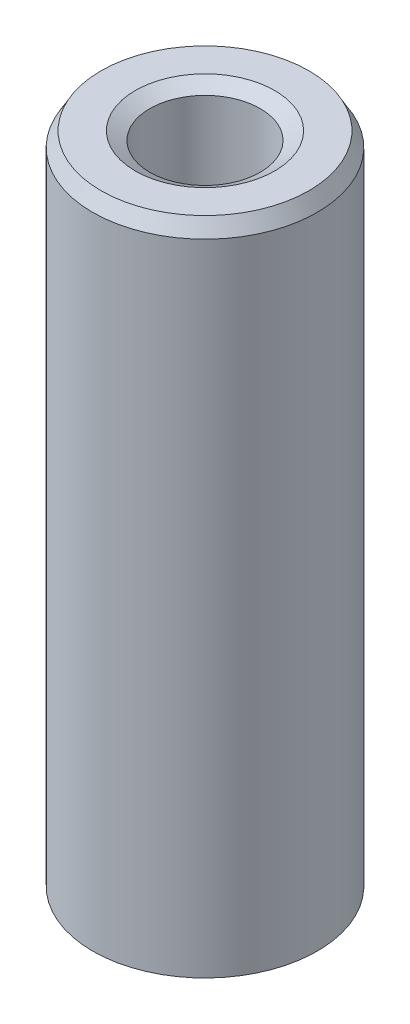
SolidWorks part; units mm, degrees
ref_plane "Front Plane" through (0, 0, 0) normal (0, 0, 1) x (1, 0, 0)
ref_plane "Top Plane" through (0, 0, 0) normal (0, 1, 0) x (1, 0, 0)
ref_plane "Right Plane" through (0, 0, 0) normal (1, 0, 0) x (0, 0, -1)
sketch "Sketch1" plane through (0, 0, 0) normal (0, 1, 0) x (1, 0, 0)
  circle A0 centre (0, 0) radius 20
  dimension "SLEEVE_OD" = 40
extrude "Boss-Extrude1" add sketch "Sketch1" along normal blind 118.0104
sketch "Sketch2" plane through (0, 0, 0) normal (0, 1, 0) x (1, 0, 0)
  circle A0 centre (0, 0) radius 9.8304
  dimension "BORE_D" = 19.6609
extrude "Cut-Extrude1" cut sketch "Sketch2" along normal through all
chamfer "Chamfer1" distance 2.5868 angle 30 4 edges at (0, 118.0104, 9.8304) (0, 0, 9.8304) (0, 0, 20) (0, 118.0104, 20) first distance on face at (0, 118.0104, 9.8304) first distance on face at (0, 0, 9.8304) first distance on face at (0, 118.0104, 20)
